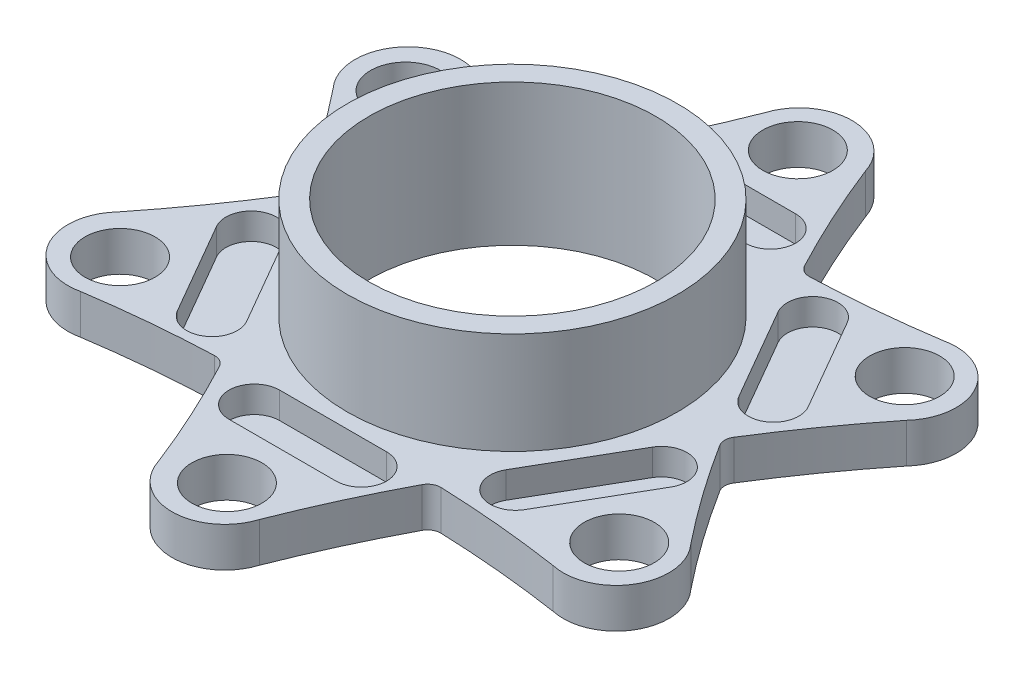
SolidWorks part; units mm, degrees
note: '?' marks a value the reader was unsure of.
ref_plane "Front Plane" through (0, 0, 0) normal (0, 0, 1) x (1, 0, 0)
ref_plane "Top Plane" through (0, 0, 0) normal (0, 1, 0) x (1, 0, 0)
ref_plane "Right Plane" through (0, 0, 0) normal (1, 0, 0) x (0, 0, -1)
sketch "Sketch1" plane through (0, 0, 0) normal (0, 1, 0) x (1, 0, 0)
  circle A0 centre (0, 0) radius 31.75
  dimension "D1" = 63.5
extrude "CenterCircleExtrude" add sketch "Sketch1" along normal blind 19.558 contours A0
sketch "Sketch2" plane through (0, 0, 0) normal (0, -1, 0) x (1, 0, 0)
  circle A0 centre (0, 0) radius 80.01
  dimension "D1" = 160.02
extrude "BaseExpand" add sketch "Sketch2" along normal blind 7.62
sketch "Sketch3" plane through (0, 19.558, 0) normal (0, 1, 0) x (1, 0, 0)
  circle A0 centre (0, 0) radius 27.559
  dimension "D1" = 55.118
extrude "CenterCut" cut sketch "Sketch3" against normal blind 27.178 contours A0
sketch "Sketch4" plane through (0, 0, 0) normal (0, 1, 0) x (1, 0, 0)
  circle A0 centre (-0.2611, 55.1174) radius 6.731
  circle A6 centre (47.6025, 27.7848) radius 6.731
  circle A7 centre (47.8636, -27.3325) radius 6.731
  circle A8 centre (0.2611, -55.1174) radius 6.731
  circle A9 centre (-47.6025, -27.7848) radius 6.731
  circle A10 centre (-47.8636, 27.3325) radius 6.731
  point P14 (-0.2611, -0.0003)
  point P28 (0, 0)
  dimension "D1" = 13.462
  dimension "D2" = 55.118
  dimension "D4" = 6
extrude "OuterCircleCut" cut sketch "Sketch4" against normal blind 7.62
sketch "Sketch8" plane through (0, 0, 0) normal (0, 1, 0) x (1, 0, 0)
  line L4 (0, -44.5914) -> (0, -31.75) construction
  line L6 (0, -14.9479) -> (0, 14.9479) construction
  line L8 (0, 0) -> (10.16, 55.118) construction
  line L9 (10.16, 55.118) -> (-10.16, 55.118) construction
  circle A1 centre (0, 55.118) radius 10.16
  arc A6 (20.3662, 35.131) -> (9.6916, 58.1672) centre (205.1961, 134.7692) cw
  arc A7 (-20.2607, 35.327) -> (-9.6916, 58.1672) centre (-205.1961, 134.7692) ccw
  arc A8 (20.3662, 35.131) -> (46.7444, 37.6011) centre (14.018, 245.0109) ccw
  circle A9 centre (47.6361, 27.4803) radius 10.16
  arc A10 (40.51, -0.1509) -> (55.9551, 21.6476) centre (219.2142, -110.3992) cw
  arc A11 (40.51, -0.1509) -> (55.8382, -21.76) centre (219.0972, 110.2867) ccw
  circle A12 centre (47.5192, -27.5927) radius 10.16
  arc A13 (20.0268, -35.2368) -> (46.6274, -37.7135) centre (13.9011, -245.1233) cw
  arc A14 (20.0268, -35.2368) -> (8.9769, -59.316) centre (204.9622, -134.6791) ccw
  circle A15 centre (-0.2339, -55.0279) radius 10.16
  arc A16 (-20.6001, -35.0409) -> (-9.4446, -59.316) centre (-205.43, -134.6791) cw
  arc A17 (-20.6001, -35.0409) -> (-46.9782, -37.5109) centre (-14.2519, -244.9208) ccw
  circle A18 centre (-47.87, -27.3901) radius 10.16
  arc A19 (-40.7438, 0.241) -> (-56.189, -21.5575) centre (-219.448, 110.4893) cw
  arc A20 (-40.7438, 0.241) -> (-56.072, 21.8501) centre (-219.3311, -110.1966) ccw
  circle A21 centre (-47.753, 27.6828) radius 10.16
  arc A22 (-20.2607, 35.327) -> (-46.8613, 37.8036) centre (-14.135, 245.2135) cw
  point P14 (0, 0)
  point P27 (0, 0)
  point P63 (0, 0)
  point P72 (0, 0)
  point P74 (-0.1169, 0.0451)
  dimension "D1" = 6
extrude "StarfishCut" cut sketch "Sketch8" against normal blind 7.62
sketch "Sketch14" plane through (0, 0, 0) normal (0, 1, 0) x (1, 0, 0)
  line L0 (35.0186, 8.5208) -> (24.7426, 26.3193)
  line L4 (43.446, 13.3864) -> (33.1701, 31.1849)
  line L8 (39.2323, 10.9536) -> (28.9564, 28.7521) construction
  line L11 (24.8885, -26.0665) -> (35.1645, -8.2681)
  line L14 (33.316, -30.9322) -> (43.592, -13.1337)
  line L17 (29.1023, -28.4994) -> (39.3782, -10.7009) construction
  line L24 (-10.13, -34.5874) -> (10.4219, -34.5874)
  line L27 (10.13, 39.453) -> (-10.4219, 39.453) construction
  line L28 (10.13, 34.5874) -> (-10.4219, 34.5874)
  line L29 (10.13, 44.3186) -> (-10.4219, 44.3186)
  line L30 (-10.13, -44.3186) -> (10.4219, -44.3186)
  line L33 (-10.13, -39.453) -> (10.4219, -39.453) construction
  line L36 (-35.0186, -8.5208) -> (-24.7426, -26.3193)
  line L37 (-43.446, -13.3864) -> (-33.1701, -31.1849)
  line L38 (-39.2323, -10.9536) -> (-28.9564, -28.7521) construction
  line L39 (-24.8885, 26.0665) -> (-35.1645, 8.2681)
  line L40 (-33.316, 30.9322) -> (-43.592, 13.1337)
  line L41 (-29.1023, 28.4994) -> (-39.3782, 10.7009) construction
  arc A78 (10.13, 34.5874) -> (10.13, 44.3186) centre (10.13, 39.453) ccw
  arc A79 (-10.4219, 44.3186) -> (-10.4219, 34.5874) centre (-10.4219, 39.453) ccw
  arc A84 (33.1701, 31.1849) -> (24.7426, 26.3193) centre (28.9564, 28.7521) ccw
  arc A85 (35.0186, 8.5208) -> (43.446, 13.3864) centre (39.2323, 10.9536) ccw
  arc A86 (43.592, -13.1337) -> (35.1645, -8.2681) centre (39.3782, -10.7009) ccw
  arc A87 (24.8885, -26.0665) -> (33.316, -30.9322) centre (29.1023, -28.4994) ccw
  arc A88 (10.4219, -44.3186) -> (10.4219, -34.5874) centre (10.4219, -39.453) ccw
  arc A89 (-10.13, -34.5874) -> (-10.13, -44.3186) centre (-10.13, -39.453) ccw
  arc A90 (-33.1701, -31.1849) -> (-24.7426, -26.3193) centre (-28.9564, -28.7521) ccw
  arc A91 (-35.0186, -8.5208) -> (-43.446, -13.3864) centre (-39.2323, -10.9536) ccw
  arc A92 (-43.592, 13.1337) -> (-35.1645, 8.2681) centre (-39.3782, 10.7009) ccw
  arc A93 (-24.8885, 26.0665) -> (-33.316, 30.9322) centre (-29.1023, 28.4994) ccw
  point P4 (34.0943, 19.8529)
  point P11 (34.2402, -19.6001)
  point P12 (-37.8101, 12.2891)
  point P19 (0.1459, -39.453)
  point P22 (-0.1459, 39.453)
  point P33 (-34.0943, -19.8529)
  point P34 (0, 0)
  point P41 (-34.2402, 19.6001)
  point P42 (0, 0)
  point P47 (0, 0)
  point P51 (0.0346, -0.0647)
  point P61 (0, 0)
  point P62 (37.8123, 12.2821)
  point P69 (23.3657, -32.1663)
  point P93 (0, 0)
  point P97 (0, 0)
  dimension "D1" = 6
extrude "Batman Cut" cut sketch "Sketch14" against normal blind 5.08
ref_axis "Axis1" through (0, -7.62, 0) along (0, 1, 0)?
fillet "Fillet1" radius 2.54 6 edges at (20.3662, -3.81, -35.131) (-20.2607, -3.81, -35.327) (-40.7438, -3.81, -0.241) (-20.6001, -3.81, 35.0409) (20.0268, -3.81, 35.2368) (40.51, -3.81, 0.1509)
